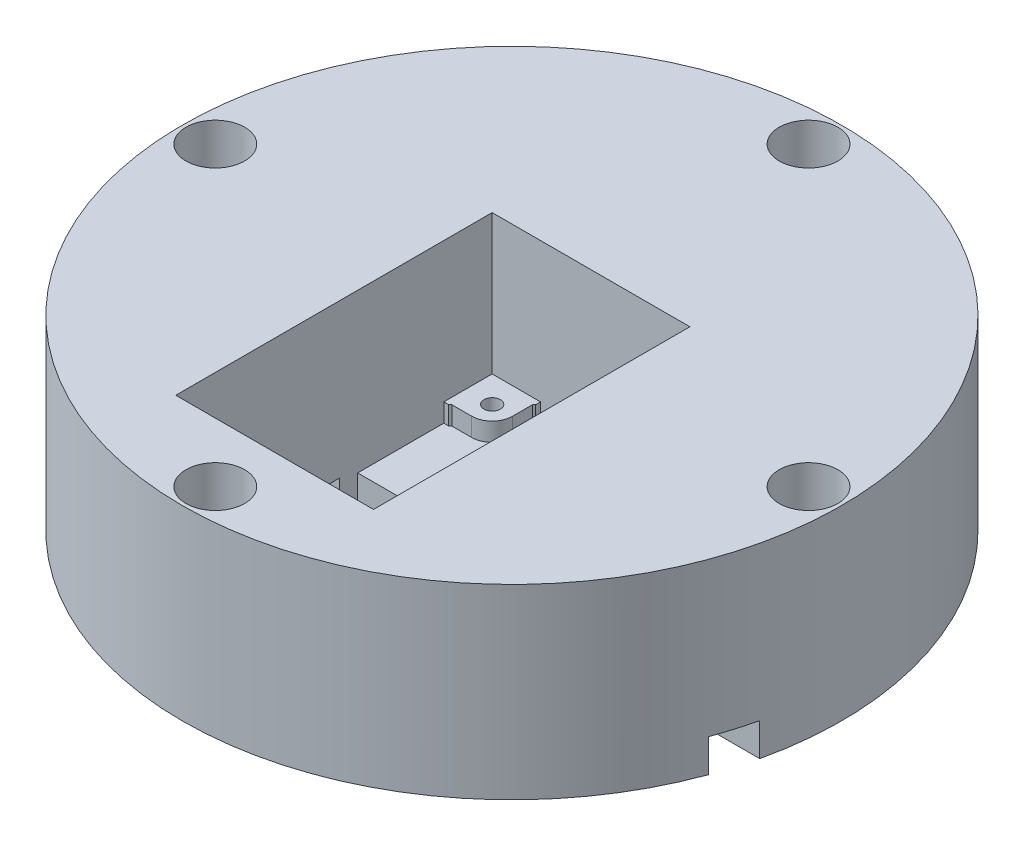
SolidWorks part; units mm, degrees
ref_plane "정면도" through (0, 0, 0) normal (0, 0, 1) x (1, 0, 0)
ref_plane "평면도" through (0, 0, 0) normal (0, 1, 0) x (1, 0, 0)
ref_plane "우측면도" through (0, 0, 0) normal (1, 0, 0) x (0, 0, -1)
sketch "스케치1" plane through (0, 0, 0) normal (0, 1, 0) x (1, 0, 0)
  circle A0 centre (0, 0) radius 95
  dimension "D1" = 190
extrude "보스-돌출1" add sketch "스케치1" along normal blind 20
sketch "스케치3" plane through (0, 20, 0) normal (0, 1, 0) x (1, 0, 0)
  line L1 (-15, 12) -> (15, 12)
  line L2 (-15, 12) -> (-15, -36)
  line L3 (-15, -36) -> (15, -36)
  line L4 (15, 12) -> (15, -36)
  line L11 (-14.25, -28.6621) -> (-14.25, -33.25)
  line L12 (-12.25, -35.25) -> (-14.25, -33.25)
  line L13 (-12.25, -35.25) -> (-7.6621, -35.25)
  line L15 (7.6621, -35.25) -> (12.25, -35.25)
  line L16 (14.25, -33.25) -> (13.7177, -33.7823)
  line L17 (14.25, -33.25) -> (14.25, -28.6621)
  line L21 (14.25, 4.6621) -> (14.25, 9.25)
  line L22 (12.25, 11.25) -> (14.25, 9.25)
  line L23 (12.25, 11.25) -> (7.6621, 11.25)
  line L27 (-7.6621, 11.25) -> (-12.25, 11.25)
  line L28 (-14.25, 9.25) -> (-12.25, 11.25)
  line L29 (-14.25, 9.25) -> (-14.25, 4.6621)
  line L31 (12.7823, -34.7177) -> (12.25, -35.25)
  line L32 (-13.95, 4.75) -> (-14.25, 4.45) construction
  line L33 (-13.95, 4.75) -> (-11, 4.75) construction
  line L34 (-7.75, 10.95) -> (-7.75, 8) construction
  line L35 (-7.45, 11.25) -> (-7.75, 10.95) construction
  line L36 (14.25, 4.45) -> (13.95, 4.75) construction
  line L37 (13.95, 4.75) -> (11, 4.75) construction
  line L38 (7.75, 10.95) -> (7.75, 8) construction
  line L39 (7.75, 10.95) -> (7.45, 11.25) construction
  line L40 (13.95, -28.75) -> (14.25, -28.45) construction
  line L41 (7.45, -35.25) -> (7.75, -34.95) construction
  line L42 (7.75, -34.95) -> (7.75, -32) construction
  line L43 (13.95, -28.75) -> (11, -28.75) construction
  line L44 (-14.25, -28.45) -> (-13.95, -28.75) construction
  line L45 (-7.75, -34.95) -> (-7.45, -35.25) construction
  line L46 (-7.75, -34.95) -> (-7.75, -32) construction
  line L47 (-13.95, -28.75) -> (-11, -28.75) construction
  line L48 (-7.6621, 11.25) -> (-7.9, 11.0121)
  line L49 (-7.9, 11.0121) -> (-7.9, 8)
  line L50 (-14.0121, 4.9) -> (-11, 4.9)
  line L51 (-14.0121, 4.9) -> (-14.25, 4.6621)
  line L52 (14.25, 4.6621) -> (14.0121, 4.9)
  line L53 (14.0121, 4.9) -> (11, 4.9)
  line L54 (7.9, 11.0121) -> (7.9, 8)
  line L55 (7.9, 11.0121) -> (7.6621, 11.25)
  line L56 (14.0121, -28.9) -> (14.25, -28.6621)
  line L57 (14.0121, -28.9) -> (11, -28.9)
  line L58 (7.9, -35.0121) -> (7.9, -32)
  line L59 (7.6621, -35.25) -> (7.9, -35.0121)
  line L60 (-7.9, -35.0121) -> (-7.6621, -35.25)
  line L61 (-7.9, -35.0121) -> (-7.9, -32)
  line L62 (-14.0121, -28.9) -> (-11, -28.9)
  line L63 (-14.25, -28.6621) -> (-14.0121, -28.9)
  line L64 (-7.5561, 11.3561) -> (-7.9, 11.0121) construction
  line L65 (-7.6621, 11.25) -> (-7.6621, 12)
  line L66 (7.9, 11.0121) -> (7.5561, 11.3561) construction
  line L67 (7.6621, 11.25) -> (7.6621, 12)
  line L68 (-14.0121, 4.9) -> (-14.3561, 4.5561) construction
  line L69 (-14.25, 4.6621) -> (-15, 4.6621)
  line L70 (14.3561, 4.5561) -> (14.0121, 4.9) construction
  line L71 (14.25, 4.6621) -> (15, 4.6621)
  line L72 (14.0121, -28.9) -> (14.3561, -28.5561) construction
  line L73 (14.25, -28.6621) -> (15, -28.6621)
  line L74 (7.5561, -35.3561) -> (7.9, -35.0121) construction
  line L75 (7.6621, -35.25) -> (7.6621, -36)
  line L76 (-7.9, -35.0121) -> (-7.5561, -35.3561) construction
  line L77 (-7.6621, -35.25) -> (-7.6621, -36)
  line L78 (-14.3561, -28.5561) -> (-14.0121, -28.9) construction
  line L79 (-14.25, -28.6621) -> (-15, -28.6621)
  arc A0 (13.6369, -33.8998) -> (13.7177, -33.7823) centre (11, -32) ccw
  arc A1 (12.7823, -34.7177) -> (12.9067, -34.6319) centre (11, -32) ccw
  arc A2 (12.9067, -34.6319) -> (13.6369, -33.8998) centre (11, -32) ccw
  circle A3 centre (0, 0) radius 10.4 construction
  arc A4 (-11, 4.75) -> (-9.6585, 5.0398) centre (-11, 8) ccw construction
  arc A5 (-9.6585, 5.0398) -> (-7.7705, 7.6358) centre (-11, 8) ccw construction
  arc A6 (-7.7705, 7.6358) -> (-7.75, 8) centre (-11, 8) ccw construction
  arc A7 (9.6585, 5.0398) -> (11, 4.75) centre (11, 8) ccw construction
  arc A8 (7.7705, 7.6358) -> (9.6585, 5.0398) centre (11, 8) ccw construction
  arc A9 (7.75, 8) -> (7.7705, 7.6358) centre (11, 8) ccw construction
  arc A10 (11, -28.75) -> (7.75, -32) centre (11, -32) ccw construction
  arc A11 (-7.75, -32) -> (-11, -28.75) centre (-11, -32) ccw construction
  arc A12 (12.25, 8) -> (9.75, 8) centre (11, 8) ccw construction
  arc A13 (9.75, -32) -> (12.25, -32) centre (11, -32) ccw construction
  arc A14 (-7.9195, 7.6526) -> (-7.9, 8) centre (-11, 8) ccw
  arc A15 (-9.7204, 5.1764) -> (-7.9195, 7.6526) centre (-11, 8) ccw
  arc A16 (-11, 4.9) -> (-9.7204, 5.1764) centre (-11, 8) ccw
  arc A17 (9.7204, 5.1764) -> (11, 4.9) centre (11, 8) ccw
  arc A18 (7.9195, 7.6526) -> (9.7204, 5.1764) centre (11, 8) ccw
  arc A19 (7.9, 8) -> (7.9195, 7.6526) centre (11, 8) ccw
  arc A20 (11, -28.9) -> (7.9, -32) centre (11, -32) ccw
  arc A21 (-7.9, -32) -> (-11, -28.9) centre (-11, -32) ccw
  circle A22 centre (-11, 8) radius 1.25
  circle A23 centre (11, 8) radius 1.25
  circle A24 centre (-11, -32) radius 1.25
  circle A25 centre (11, -32) radius 1.25
  spline S0 degree 2 poles (-12.25, 8) (-12.25, 8.2489) (-12.1548, 8.4784) (-12.0594, 8.7085) (-11.8839, 8.8839) (-11.7076, 9.06) (-11.4784, 9.1548) (-11.2481, 9.2501) (-11, 9.25) (-10.7508, 9.2499) (-10.5216, 9.1548) (-10.2915, 9.0594) (-10.1161, 8.8839) (-9.94, 8.7076) (-9.8452, 8.4784) (-9.75, 8.2484) (-9.75, 8) knots 0 0 0 0.125 0.125 0.25 0.25 0.375 0.375 0.5 0.5 0.625 0.625 0.75 0.75 0.875 0.875 1 1 1 construction
  spline S1 degree 2 poles (-9.75, 8) (-9.75, 7.7511) (-9.8452, 7.5216) (-9.9406, 7.2915) (-10.1161, 7.1161) (-10.2924, 6.94) (-10.5216, 6.8452) (-10.7519, 6.7499) (-11, 6.75) (-11.2492, 6.7501) (-11.4784, 6.8452) (-11.7085, 6.9406) (-11.8839, 7.1161) (-12.06, 7.2924) (-12.1548, 7.5216) (-12.25, 7.7516) (-12.25, 8) knots 0 0 0 0.125 0.125 0.25 0.25 0.375 0.375 0.5 0.5 0.625 0.625 0.75 0.75 0.875 0.875 1 1 1 construction
  spline S2 degree 2 poles (-12.25, -32) (-12.25, -31.7511) (-12.1548, -31.5216) (-12.0594, -31.2915) (-11.8839, -31.1161) (-11.7076, -30.94) (-11.4784, -30.8452) (-11.2481, -30.7499) (-11, -30.75) (-10.7508, -30.7501) (-10.5216, -30.8452) (-10.2915, -30.9406) (-10.1161, -31.1161) (-9.94, -31.2924) (-9.8452, -31.5216) (-9.75, -31.7516) (-9.75, -32) knots 0 0 0 0.125 0.125 0.25 0.25 0.375 0.375 0.5 0.5 0.625 0.625 0.75 0.75 0.875 0.875 1 1 1 construction
  spline S3 degree 2 poles (-9.75, -32) (-9.75, -32.2489) (-9.8452, -32.4784) (-9.9406, -32.7085) (-10.1161, -32.8839) (-10.2924, -33.06) (-10.5216, -33.1548) (-10.7519, -33.2501) (-11, -33.25) (-11.2492, -33.2499) (-11.4784, -33.1548) (-11.7085, -33.0594) (-11.8839, -32.8839) (-12.06, -32.7076) (-12.1548, -32.4784) (-12.25, -32.2484) (-12.25, -32) knots 0 0 0 0.125 0.125 0.25 0.25 0.375 0.375 0.5 0.5 0.625 0.625 0.75 0.75 0.875 0.875 1 1 1 construction
  spline S4 degree 2 poles (9.75, -32) (9.75, -31.7511) (9.8452, -31.5216) (9.9406, -31.2915) (10.1161, -31.1161) (10.2924, -30.94) (10.5216, -30.8452) (10.7519, -30.7499) (11, -30.75) (11.2492, -30.7501) (11.4784, -30.8452) (11.7085, -30.9406) (11.8839, -31.1161) (12.06, -31.2924) (12.1548, -31.5216) (12.25, -31.7516) (12.25, -32) knots 0 0 0 0.125 0.125 0.25 0.25 0.375 0.375 0.5 0.5 0.625 0.625 0.75 0.75 0.875 0.875 1 1 1 construction
  spline S5 degree 2 poles (12.25, 8) (12.25, 7.7511) (12.1548, 7.5216) (12.0594, 7.2915) (11.8839, 7.1161) (11.7076, 6.94) (11.4784, 6.8452) (11.2481, 6.7499) (11, 6.75) (10.7508, 6.7501) (10.5216, 6.8452) (10.2915, 6.9406) (10.1161, 7.1161) (9.94, 7.2924) (9.8452, 7.5216) (9.75, 7.7516) (9.75, 8) knots 0 0 0 0.125 0.125 0.25 0.25 0.375 0.375 0.5 0.5 0.625 0.625 0.75 0.75 0.875 0.875 1 1 1 construction
  dimension "D9" = 2.5
  dimension "D1" = 30
  dimension "D2" = 48
  dimension "D3" = 0.75
  dimension "D4" = 0.75
  dimension "D5" = 0.15
  dimension "D6" = 0.15
  dimension "D7" = 0.15
  dimension "D8" = 0.15
extrude "컷-돌출1" cut sketch "스케치3" against normal blind 10 contours A11 L46 L45 L41 L42 A10 L43 L40 L36 L37 A7 A8 A3 A5 A4 L33 L32 L44 L47 | A9 L38 L39 L35 L34 A6 A5 A3 A8 | A8 A3 A5 | A21 L61 L60 L77 L3 L75 L59 L58 A20 L57 L56 L73 L4 L71 L52 L53 A17 A18 A19 L54 L55 L67 L1 L65 L48 L49 A14 A15 A16 L50 L51 L69 L2 L79 L63 L62 region at (0, 20, 12)
extrude "컷-돌출3" cut sketch "스케치3<3>" against normal through all and the other way through all contours S3 S2 | S4 A13 | S5 A12 | S1 S0 | A24 | A25 | A23 | A22
sketch "스케치3<3>" plane through (0, 20, 0) normal (0, 1, 0) x (1, 0, 0) same geometry as "스케치3"
extrude "컷-돌출4" cut sketch "스케치3<4>" against normal blind 7.2 and the other way through all contours A5 A6 L34 L35 L27 L28 L29 L32 L33 A4 A3 S0 S1 | A3 A5 | L38 A9 A8 A3 A7 L37 L36 L21 L22 L23 L39 A12 S5 | A3 A8 | L43 A10 L42 L41 L15 L31 A1 A2 A0 L16 L17 L40 A13 S4 | L46 A11 L47 L44 L11 L12 L13 L45 S2 S3 | L69 L29 L28 L27 L65 L1 L2 | L21 L71 L4 L1 L67 L23 L22 | L11 L79 L2 L3 L77 L13 L12 | A2 A1 L31 L15 L75 L3 L4 L73 L17 L16 A0 region at (-11.3311, 20, -11.8962) region at (11.3311, 20, -11.8962) region at (-7.8469, 20, -11.1969) region at (-14.625, 20, 28.7659) region at (9.9561, 20, -11.1568) region at (-14.1969, 20, 28.8469) region at (14.8962, 20, 32.3311) region at (14.1568, 20, 30.9561)
sketch "스케치3<4>" plane through (0, 20, 0) normal (0, 1, 0) x (1, 0, 0) same geometry as "스케치3"
sketch "스케치4" plane through (0, 0, 0) normal (0, -1, 0) x (1, 0, 0)
  circle A0 centre (11, -8) radius 2.4
  circle A3 centre (11, 32) radius 2.4
  circle A4 centre (-11, -8) radius 2.4
  circle A5 centre (-11, 32) radius 2.4
  spline S5 degree 2 poles (-12.25, 32) (-12.25, 31.7511) (-12.1548, 31.5216) (-12.0594, 31.2915) (-11.8839, 31.1161) (-11.7076, 30.94) (-11.4784, 30.8452) (-11.2481, 30.7499) (-11, 30.75) (-10.7508, 30.7501) (-10.5216, 30.8452) (-10.2915, 30.9406) (-10.1161, 31.1161) (-9.94, 31.2924) (-9.8452, 31.5216) (-9.75, 31.7516) (-9.75, 32) knots 0 0 0 0.125 0.125 0.25 0.25 0.375 0.375 0.5 0.5 0.625 0.625 0.75 0.75 0.875 0.875 1 1 1 construction
  spline S7 degree 2 poles (-9.75, 32) (-9.75, 32.2489) (-9.8452, 32.4784) (-9.9406, 32.7085) (-10.1161, 32.8839) (-10.2924, 33.06) (-10.5216, 33.1548) (-10.7519, 33.2501) (-11, 33.25) (-11.2492, 33.2499) (-11.4784, 33.1548) (-11.7085, 33.0594) (-11.8839, 32.8839) (-12.06, 32.7076) (-12.1548, 32.4784) (-12.25, 32.2484) (-12.25, 32) knots 0 0 0 0.125 0.125 0.25 0.25 0.375 0.375 0.5 0.5 0.625 0.625 0.75 0.75 0.875 0.875 1 1 1 construction
  dimension "D1" = 4.8
  dimension "D2" = 2
extrude "컷-돌출5" cut sketch "스케치4" against normal blind 2.6
sketch "스케치5" plane through (0, 0, 0) normal (0, -1, 0) x (1, 0, 0)
  circle A0 centre (0, 0) radius 86 construction
  circle A1 centre (86, 0) radius 4
  circle A2 centre (0, -86) radius 4
  circle A3 centre (-86, 0) radius 4
  circle A4 centre (0, 86) radius 4
  dimension "D1" = 172
  dimension "D2" = 8
extrude "컷-돌출6" cut sketch "스케치5" against normal through all contours A1 | A2 | A3 | A4
sketch "스케치6" plane through (0, 0, 0) normal (0, 1, 0) x (1, 0, 0)
  line L1 (-15, -8.4) -> (15, -8.4)
  line L2 (-15, -8.4) -> (-15, -19.9)
  line L3 (-15, -19.9) -> (15, -19.9)
  line L4 (15, -8.4) -> (15, -19.9)
  line L7 (-15, -36) -> (15, -36) construction
  line L8 (-15, 12) -> (-15, -36) construction
  line L9 (15, 12) -> (15, -36) construction
  dimension "D1" = 16.1
  dimension "D2" = 11.5
extrude "컷-돌출7" cut sketch "스케치6" along normal through all
sketch "스케치7" plane through (0, 0, 0) normal (0, -1, 0) x (1, 0, 0)
  line L0 (-15, 8.4) -> (-15, 19.9) construction
  line L1 (15, 8.4) -> (-15, 8.4) construction
  line L2 (-15, 19.9) -> (15, 19.9) construction
  line L3 (15, 19.9) -> (15, 8.4) construction
  line L4 (-15, 8.4) -> (-15, 19.9)
  line L5 (15, 8.4) -> (-15, 8.4)
  line L6 (-15, 19.9) -> (15, 19.9)
  line L7 (15, 19.9) -> (15, 8.4)
  circle A0 centre (-86, 0) radius 4 construction
  circle A1 centre (0, 0) radius 95
  circle A2 centre (0, 0) radius 95
  circle A3 centre (0, 86) radius 4 construction
  circle A4 centre (86, 0) radius 4 construction
  circle A5 centre (0, -86) radius 4 construction
  circle A6 centre (-86, 0) radius 4
  circle A7 centre (0, 86) radius 4
  circle A8 centre (86, 0) radius 4
  circle A9 centre (0, -86) radius 4
  circle A10 centre (11, -8) radius 2.4 construction
  circle A11 centre (-11, -8) radius 2.4 construction
  circle A12 centre (-11, 32) radius 2.4 construction
  circle A13 centre (11, 32) radius 2.4 construction
  circle A14 centre (11, -8) radius 2.4
  circle A15 centre (-11, -8) radius 2.4
  circle A16 centre (-11, 32) radius 2.4
  circle A17 centre (11, 32) radius 2.4
  dimension "D1" = 0
extrude "보스-돌출2" add sketch "스케치7" along normal blind 1.3
sketch "스케치8" plane through (0, 2.6, 0) normal (0, -1, 0) x (1, 0, 0)
  circle A0 centre (-11, -8) radius 2.4 construction
  circle A1 centre (11, -8) radius 2.4 construction
  circle A2 centre (11, 32) radius 2.4 construction
  circle A3 centre (-11, 32) radius 2.4 construction
  circle A4 centre (-11, -8) radius 2.4
  circle A5 centre (11, -8) radius 2.4
  circle A6 centre (11, 32) radius 2.4
  circle A7 centre (-11, 32) radius 2.4
  circle A8 centre (-11, -8) radius 1.25 construction
  circle A9 centre (11, -8) radius 1.25 construction
  circle A10 centre (11, 32) radius 1.25 construction
  circle A11 centre (-11, 32) radius 1.25 construction
  circle A12 centre (-11, -8) radius 1.25
  circle A13 centre (11, -8) radius 1.25
  circle A14 centre (11, 32) radius 1.25
  circle A15 centre (-11, 32) radius 1.25
extrude "보스-돌출3" add sketch "스케치8" along normal blind 1.3
sketch "스케치9" plane through (0, -1.3, 0) normal (0, -1, 0) x (1, 0, 0)
  line L0 (7.5, 86) -> (3.75, 92.4952)
  line L1 (-86, 7.5) -> (-92.4952, 3.75)
  line L2 (-92.4952, 3.75) -> (-92.4952, -3.75)
  line L3 (-92.4952, -3.75) -> (-86, -7.5)
  line L4 (-86, -7.5) -> (-79.5048, -3.75)
  line L5 (-79.5048, -3.75) -> (-79.5048, 3.75)
  line L6 (-79.5048, 3.75) -> (-86, 7.5)
  line L7 (3.75, 92.4952) -> (-3.75, 92.4952)
  line L8 (-3.75, 92.4952) -> (-7.5, 86)
  line L9 (-7.5, 86) -> (-3.75, 79.5048)
  line L10 (-3.75, 79.5048) -> (3.75, 79.5048)
  line L11 (3.75, 79.5048) -> (7.5, 86)
  line L12 (86, -7.5) -> (92.4952, -3.75)
  line L13 (92.4952, -3.75) -> (92.4952, 3.75)
  line L14 (92.4952, 3.75) -> (86, 7.5)
  line L15 (86, 7.5) -> (79.5048, 3.75)
  line L16 (79.5048, 3.75) -> (79.5048, -3.75)
  line L17 (79.5048, -3.75) -> (86, -7.5)
  line L18 (-7.5, -86) -> (-3.75, -92.4952)
  line L19 (-3.75, -92.4952) -> (3.75, -92.4952)
  line L20 (3.75, -92.4952) -> (7.5, -86)
  line L21 (7.5, -86) -> (3.75, -79.5048)
  line L22 (3.75, -79.5048) -> (-3.75, -79.5048)
  line L23 (-3.75, -79.5048) -> (-7.5, -86)
  circle A0 centre (-86, 0) radius 4 construction
  circle A1 centre (-86, 0) radius 4 construction
  circle A2 centre (-86, 0) radius 6.4952 construction
  point P31 (0, 0)
  dimension "D1" = 15
  dimension "D2" = 4
extrude "컷-돌출8" cut sketch "스케치9" against normal blind 6.5
sketch "스케치10" plane through (0, 20, 0) normal (0, 1, 0) x (1, 0, 0)
  circle A0 centre (0, 0) radius 50
  circle A1 centre (0, 0) radius 95 construction
  circle A2 centre (0, 0) radius 95
  circle M1 centre (86, 0) radius 4
  circle M2 centre (0, 86) radius 4
  circle M3 centre (-86, 0) radius 4
  circle M4 centre (0, -86) radius 4
  circle M9 centre (0, 0) radius 95
  dimension "D1" = 100
extrude "컷-돌출9" cut sketch "스케치10" against normal through all contours A0 M9 M2 M4 M3 M1 region at (-92.313, 20, 0)
sketch "스케치11" plane through (0, 20, 0) normal (0, 1, 0) x (1, 0, 0)
  circle A0 centre (0, 45) radius 2.5
  circle A1 centre (0, 0) radius 45 construction
  circle A2 centre (45, 0) radius 2.5
  circle A3 centre (0, -45) radius 2.5
  circle A4 centre (-45, 0) radius 2.5
  point P14 (0, 0)
  dimension "D1" = 5
  dimension "D2" = 90
  dimension "D3" = 4
extrude "컷-돌출10" cut sketch "스케치11" against normal through all
sketch "스케치12" plane through (0, -1.3, 0) normal (0, -1, 0) x (1, 0, 0)
  circle A0 centre (0, -45) radius 4.45
  circle A1 centre (-45, 0) radius 4.45
  circle A2 centre (0, 45) radius 4.45
  circle A3 centre (45, 0) radius 4.45
  point P12 (0, 0)
  dimension "D1" = 8.9
  dimension "D2" = 4
extrude "컷-돌출11" cut sketch "스케치12" against normal blind 6.3 contours A0 | A3 | A2 | A1
sketch "스케치13" plane through (0, 20, 0) normal (0, 1, 0) x (1, 0, 0)
  line L0 (-15, -36) -> (15, -36) construction
  line L1 (15, 12) -> (15, -36) construction
  line L2 (-15, 12) -> (15, 12) construction
  line L3 (-15, 12) -> (-15, -36) construction
  line L4 (-15, -36) -> (15, -36)
  line L5 (15, 12) -> (15, -36)
  line L6 (-15, 12) -> (15, 12)
  line L7 (-15, 12) -> (-15, -36)
  circle A0 centre (0, 45) radius 2.5 construction
  circle A1 centre (0, 0) radius 50
  circle A2 centre (0, 0) radius 50
  circle A3 centre (-45, 0) radius 2.5 construction
  circle A4 centre (0, -45) radius 2.5 construction
  circle A5 centre (45, 0) radius 2.5 construction
  circle A6 centre (0, 45) radius 2.5
  circle A7 centre (-45, 0) radius 2.5
  circle A8 centre (0, -45) radius 2.5
  circle A9 centre (45, 0) radius 2.5
  dimension "D1" = 0
extrude "보스-돌출4" add sketch "스케치13" along normal blind 24
sketch "스케치14" plane through (0, -1.3, 0) normal (0, -1, 0) x (1, 0, 0)
  circle A1 centre (0, 0) radius 50
  circle A2 centre (0, 0) radius 50
  dimension "D1" = 0
extrude "컷-돌출12" cut sketch "스케치14" against normal blind 7
sketch "스케치16" plane through (0, 5.7, 0) normal (0, -1, 0) x (1, 0, 0)
  circle A0 centre (0, -45) radius 4.45
  circle A1 centre (-45, 0) radius 4.45
  circle A2 centre (0, 45) radius 4.45
  circle A3 centre (45, 0) radius 4.45
  point P12 (0, 0)
  dimension "D1" = 8.9
  dimension "D2" = 4
sketch "스케치17" plane through (0, 5.7, 0) normal (0, -1, 0) x (1, 0, 0)
  circle A0 centre (11, -8) radius 2.4
  circle A1 centre (-11, -8) radius 2.4
  circle A2 centre (-11, 32) radius 2.4
  circle A3 centre (11, 32) radius 2.4
  dimension "D1" = 4.8
extrude "컷-돌출14" cut sketch "스케치17" against normal blind 2.6
sketch "스케치18" plane through (0, 5.7, 0) normal (0, -1, 0) x (1, 0, 0)
  line L1 (-48.7409, 17.15) -> (48.7409, 17.15)
  line L2 (-48.7409, 17.15) -> (-48.7409, 11.15)
  line L3 (-48.7409, 11.15) -> (48.7409, 11.15)
  line L4 (48.7409, 17.15) -> (48.7409, 11.15)
  line L5 (0, 11.15) -> (0, 17.15) construction
  line L6 (-48.7409, 14.15) -> (48.7409, 14.15) construction
  line L7 (15, 19.9) -> (-15, 19.9) construction
  circle A0 centre (0, 0) radius 50 construction
  point P0 (0, 14.15)
  dimension "D1" = 5.75
  dimension "D2" = 6
extrude "컷-돌출15" cut sketch "스케치18" against normal blind 5
sketch "스케치19" plane through (0, 44, 0) normal (0, 1, 0) x (1, 0, 0)
  circle A1 centre (0, 0) radius 50
  circle A2 centre (0, 0) radius 50
  dimension "D1" = 0
extrude "컷-돌출16" cut sketch "스케치19" against normal blind 10
ref_plane "평면1" through (0, 20.7, 0) normal (0, -1, 0) x (-1, 0, 0)
sketch "스케치20" plane through (0, 20.7, 0) normal (0, -1, 0) x (-1, 0, 0)
  circle A1 centre (-45, 0) radius 4.45
  circle A2 centre (-45, 0) radius 4.45
  circle A3 centre (0, -45) radius 4.45
  circle A4 centre (0, -45) radius 4.45
  circle A5 centre (45, 0) radius 4.45
  circle A6 centre (45, 0) radius 4.45
  circle A7 centre (0, 45) radius 4.45
  circle A8 centre (0, 45) radius 4.45
  dimension "D1" = 0
  dimension "D2" = 0
  dimension "D3" = 0
  dimension "D4" = 0
extrude "컷-돌출17" cut sketch "스케치20" against normal through all and the other way blind 6.3
